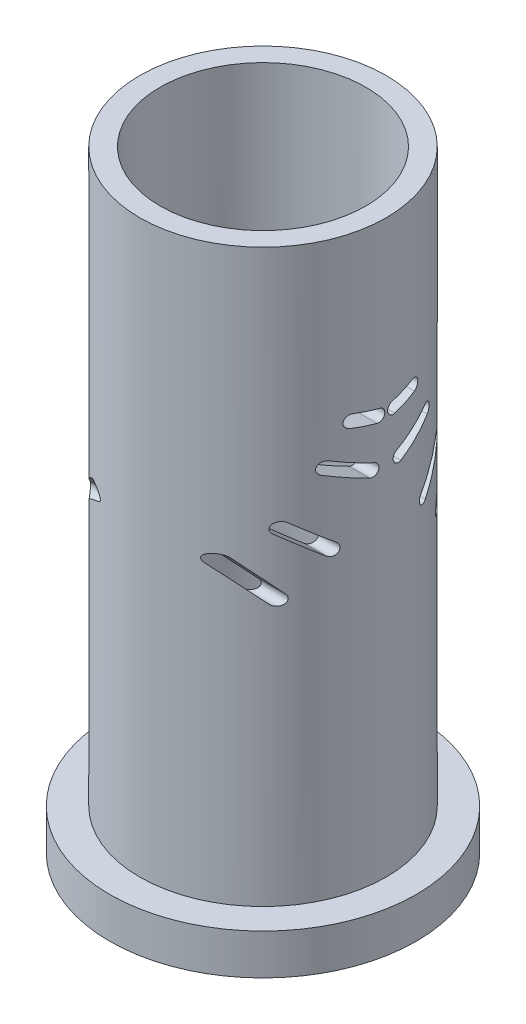
SolidWorks part; units mm, degrees
ref_plane "Front Plane" through (0, 0, 0) normal (0, 0, 1) x (1, 0, 0)
ref_plane "Top Plane" through (0, 0, 0) normal (0, 1, 0) x (1, 0, 0)
ref_plane "Right Plane" through (0, 0, 0) normal (1, 0, 0) x (0, 0, -1)
sketch "Sketch1" plane through (0, 0, 0) normal (0, 1, 0) x (1, 0, 0)
  circle A0 centre (0, 0) radius 37.75
  dimension "D1" = 75.5
extrude "Boss-Extrude1" add sketch "Sketch1" along normal blind 10
sketch "Sketch2" plane through (0, 10, 0) normal (0, 1, 0) x (1, 0, 0)
  circle A0 centre (0, 0) radius 30.35
  circle A1 centre (0, 0) radius 37.75 construction
  dimension "D1" = 7.4
extrude "Boss-Extrude2" add sketch "Sketch2" along normal blind 140.65 contours A0
sketch "Sketch4" plane through (0, 150.65, 0) normal (0, 1, 0) x (1, 0, 0)
  circle A0 centre (0, 0) radius 25.35
  circle A1 centre (0, 0) radius 30.35 construction
  dimension "D1" = 5
extrude "Cut-Extrude1" cut sketch "Sketch4" against normal blind 308.65 contours A0
ref_plane "Plane1" through (-30.35, 0, 0) normal (-1, 0, 0) x (0, 0, 1)
sketch "Sketch5" plane through (-30.35, 0, 0) normal (-1, 0, 0) x (0, 0, 1)
  line L0 (0, 10) -> (0, 73.75)
  line L1 (37.75, 10) -> (-37.75, 10) construction
  line L2 (0, 73.75) -> (-30.35, 73.75)
  line L3 (-30.35, 150.65) -> (-30.35, 10) construction
  line L4 (-30.35, 73.75) -> (30.35, 73.75)
  line L5 (30.35, 10) -> (30.35, 150.65) construction
  line L6 (0, 73.75) -> (0, 123.75)
  line L7 (0, 123.75) -> (-3.45, 123.75)
  line L8 (-3.45, 123.75) -> (3.45, 123.75)
  line L9 (20.115, 89.3433) -> (12.1758, 83.263)
  line L10 (-22.9327, 79.2646) -> (-26.23, 83.0233)
  line L11 (18.2909, 91.725) -> (10.3517, 85.6447)
  line L12 (27.3576, 82.0341) -> (20.763, 74.5167)
  line L13 (25.1024, 84.0125) -> (18.5078, 76.4951)
  line L14 (13.0565, 100.7657) -> (3.8307, 96.9078)
  line L15 (26.23, 83.0233) -> (25.1024, 84.0125)
  line L16 (-7.3884, 112.059) -> (-1.5299, 110.7633)
  line L17 (11.8992, 103.5334) -> (2.6733, 99.6756)
  line L18 (-2.1778, 107.8341) -> (-8.0362, 109.1298)
  line L19 (-11.8992, 103.5334) -> (-2.6733, 99.6756)
  line L20 (2.1778, 107.8341) -> (8.0362, 109.1298)
  line L21 (7.3884, 112.059) -> (1.5299, 110.7633)
  line L22 (-26.23, 83.0233) -> (-25.1024, 84.0125)
  line L23 (22.9327, 79.2646) -> (26.23, 83.0233)
  line L24 (-13.0565, 100.7657) -> (-3.8307, 96.9078)
  line L26 (-25.1024, 84.0125) -> (-18.5078, 76.4951)
  line L27 (-27.3576, 82.0341) -> (-20.763, 74.5167)
  line L29 (-18.2909, 91.725) -> (-10.3517, 85.6447)
  line L30 (-20.115, 89.3433) -> (-12.1758, 83.263)
  arc A0 (-30.35, 73.75) -> (-3.45, 123.75) centre (-60.6966, 122.3126) ccw
  circle A1 centre (-1.8539, 109.2987) radius 1.5
  circle A2 centre (-7.7123, 110.5944) radius 1.5
  circle A3 centre (-12.4779, 102.1496) radius 1.5
  circle A4 centre (-3.252, 98.2917) radius 1.5
  circle A5 centre (-19.2029, 90.5342) radius 1.5
  circle A6 centre (-11.2638, 84.4539) radius 1.5
  circle A7 centre (-26.23, 83.0233) radius 1.5
  circle A8 centre (-19.6354, 75.5059) radius 1.5
  circle A9 centre (19.6354, 75.5059) radius 1.5
  circle A10 centre (26.23, 83.0233) radius 1.5
  circle A11 centre (11.2638, 84.4539) radius 1.5
  circle A12 centre (19.2029, 90.5342) radius 1.5
  circle A13 centre (3.252, 98.2917) radius 1.5
  circle A14 centre (12.4779, 102.1496) radius 1.5
  circle A15 centre (7.7123, 110.5944) radius 1.5
  circle A16 centre (1.8539, 109.2987) radius 1.5
  point P27 (0, 0)
  point P89 (0, 0)
  dimension "D9" = 5
  dimension "D13" = 3
  dimension "D14" = 3
  dimension "D15" = 3
  dimension "D16" = 3
  dimension "D17" = 3
  dimension "D18" = 3
  dimension "D19" = 3
  dimension "D20" = 3
  dimension "D1" = 63.75
  dimension "D2" = 50
  dimension "D3" = 3.45
  dimension "D4" = 3.45
  dimension "D10" = 5
extrude "Cut-Extrude3" cut sketch "Sketch5" against normal blind 94 contours L22 A7 L10 | L10 A7 L22 | A7 L10 A0 L26 | A7 L27 A0 L10 | A8 L26 A0 L27 | A8 | A6 L29 A0 L30 | A5 L30 A0 L29 | A5 | A6 | A3 L24 A0 L19 | A4 L19 A0 L24 | A4 | A3 | A2 L18 A0 L16 | A1 L16 A0 L18 | A1 | A2 | A16 | L21 A16 L20 A15 | A15 | L14 A14 L17 A13 | A13 | A14 | L9 A12 L11 A11 | A12 | A11 | L12 A10 L13 A9 | A10 L15 L23 | A10 L23 L15 | A9 region at (-30.35, 77.8196, -21.665) region at (-30.35, 80.1974, -24.7944) region at (-30.35, 83.0429, -26.5295) region at (-30.35, 75.5059, -19.6354) region at (-30.35, 81.2319, -23.6151) region at (-30.35, 110.1507, -5.7059) region at (-30.35, 109.7439, -3.8669) region at (-30.35, 82.9646, -25.3316) region at (-30.35, 110.5944, -7.7123) region at (-30.35, 109.2987, -1.8539) region at (-30.35, 86.3252, -13.7072) region at (-30.35, 88.6668, -16.7647) region at (-30.35, 100.9648, -9.6445) region at (-30.35, 99.479, -6.0914) region at (-30.35, 90.5342, -19.2029) region at (-30.35, 84.4539, -11.2638) region at (-30.35, 102.1496, -12.4779) region at (-30.35, 98.2917, -3.252) region at (-30.35, 87.494, 15.2333) region at (-30.35, 90.5342, 19.2029) region at (-30.35, 84.4539, 11.2638) region at (-30.35, 83.0429, 26.5295) region at (-30.35, 78.361, 23.9627) region at (-30.35, 75.5059, 19.6354) region at (-30.35, 82.9646, 25.3316) region at (-30.35, 100.2206, 7.8649) region at (-30.35, 102.1496, 12.4779) region at (-30.35, 98.2917, 3.252) region at (-30.35, 109.9466, 4.7831) region at (-30.35, 109.2987, 1.8539) region at (-30.35, 110.5944, 7.7123)
